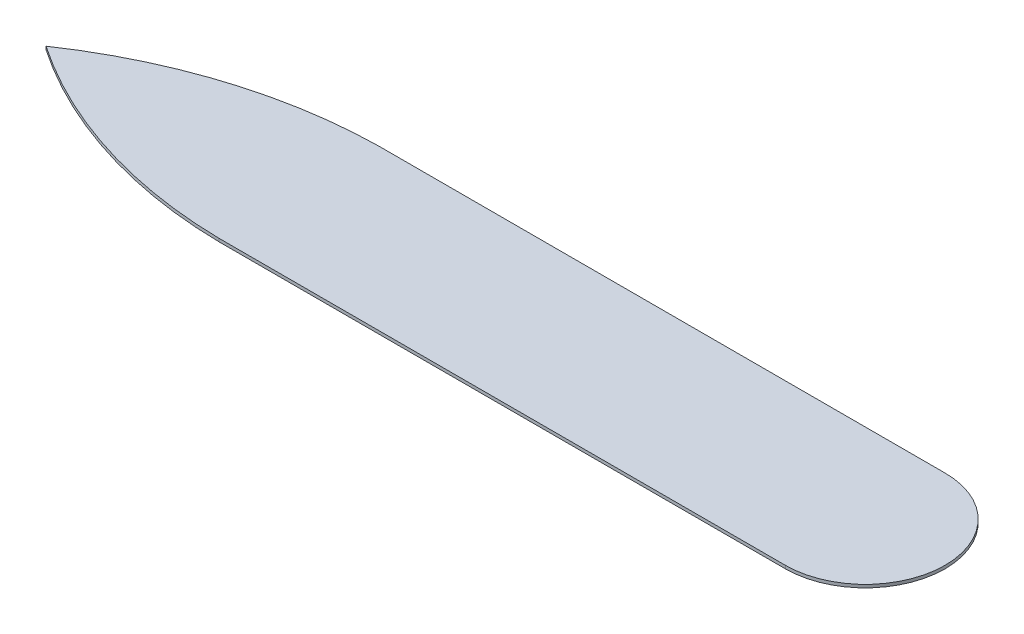
SolidWorks part; units mm, degrees
ref_plane "Front Plane" through (0, 0, 0) normal (0, 0, 1) x (1, 0, 0)
ref_plane "Top Plane" through (0, 0, 0) normal (0, 1, 0) x (1, 0, 0)
ref_plane "Right Plane" through (0, 0, 0) normal (1, 0, 0) x (0, 0, -1)
sketch "Sketch1" plane through (0, 0, 0) normal (0, 1, 0) x (1, 0, 0)
  line L0 (800, 78) -> (0, 78) construction
  line L1 (247.0699, 0) -> (800, 0)
  line L2 (0, 0) -> (0, 156) construction
  line L3 (247.0699, 156) -> (800, 156)
  arc A0 (800, 156) -> (800, 0) centre (800, 78) cw
  arc A1 (247.0699, 156) -> (0, 78) centre (253.6132, -295.0311) ccw
  arc A2 (247.0699, 0) -> (0, 78) centre (253.6132, 451.0311) cw
  dimension "D1" = 800
  dimension "D2" = 156
  dimension "D3" = 247.0699
extrude "Boss-Extrude1" add sketch "Sketch1" along normal blind 3
